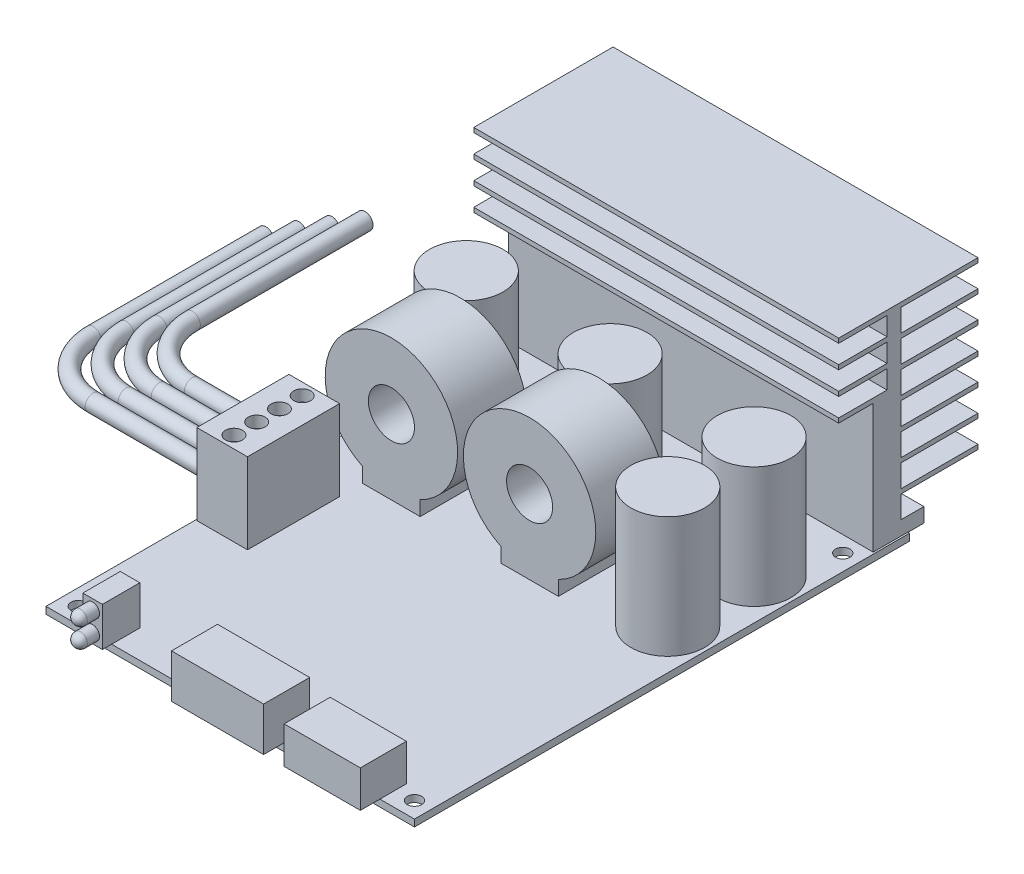
SolidWorks part; units mm, degrees
ref_plane "Front Plane" through (0, 0, 0) normal (0, 0, 1) x (1, 0, 0)
ref_plane "Top Plane" through (0, 0, 0) normal (0, 1, 0) x (1, 0, 0)
ref_plane "Right Plane" through (0, 0, 0) normal (1, 0, 0) x (0, 0, -1)
ref_plane "Plane1" through (0, 10.16, 0) normal (0, 1, 0) x (-1, 0, 0)
sketch "Sketch9" plane through (0, 0, 0) normal (0, 1, 0) x (1, 0, 0)
  line L1 (-40.64, -54.61) -> (40.64, -54.61)
  line L2 (-40.64, -54.61) -> (-40.64, 54.61)
  line L3 (-40.64, 54.61) -> (40.64, 54.61)
  line L4 (40.64, -54.61) -> (40.64, 54.61)
  circle A0 centre (37.084, -51.054) radius 1.5875
  circle A1 centre (37.084, 43.434) radius 1.5875
  circle A2 centre (-37.084, 43.434) radius 1.5875
  circle A3 centre (-37.084, -51.054) radius 1.5875
  point P4 (40.64, 0)
  point P5 (0, 54.61)
  dimension "D3" = 3.556
  dimension "D4" = 3.556
  dimension "D5" = 3.175
  dimension "D6" = 94.488
  dimension "D7" = 74.168
  dimension "D8" = 3.556
  dimension "D1" = 81.28
  dimension "D2" = 109.22
extrude "Boss-Extrude9" add sketch "Sketch9" along normal blind 1.524
sketch "Sketch2" plane through (0, 0, 0) normal (1, 0, 0) x (0, 0, -1)
  line L0 (39.37, 46.228) -> (70.104, 46.228)
  line L1 (70.104, 46.228) -> (70.104, 45.228)
  line L2 (70.104, 45.228) -> (53.086, 45.228)
  line L3 (53.086, 45.228) -> (53.086, 40.2844)
  line L4 (53.086, 40.2844) -> (70.104, 40.2844)
  line L5 (70.104, 10.5664) -> (70.104, 9.5664)
  line L6 (53.086, 4.6482) -> (58.166, 4.6482)
  line L7 (50.038, 45.228) -> (50.038, 41.1427)
  line L8 (70.104, 40.2844) -> (70.104, 39.2844)
  line L9 (70.104, 39.2844) -> (53.086, 39.2844)
  line L10 (53.086, 39.2844) -> (53.086, 34.3408)
  line L11 (53.086, 34.3408) -> (70.104, 34.3408)
  line L12 (70.104, 34.3408) -> (70.104, 33.3408)
  line L13 (70.104, 33.3408) -> (53.086, 33.3408)
  line L14 (53.086, 33.3408) -> (53.086, 28.3972)
  line L15 (53.086, 28.3972) -> (70.104, 28.3972)
  line L16 (70.104, 28.3972) -> (70.104, 27.3972)
  line L17 (70.104, 27.3972) -> (53.086, 27.3972)
  line L18 (53.086, 27.3972) -> (53.086, 22.4536)
  line L19 (53.086, 22.4536) -> (70.104, 22.4536)
  line L20 (70.104, 22.4536) -> (70.104, 21.4536)
  line L21 (70.104, 21.4536) -> (53.086, 21.4536)
  line L22 (53.086, 21.4536) -> (53.086, 16.51)
  line L23 (53.086, 16.51) -> (70.104, 16.51)
  line L24 (70.104, 16.51) -> (70.104, 15.51)
  line L25 (70.104, 15.51) -> (53.086, 15.51)
  line L26 (53.086, 15.51) -> (53.086, 10.5664)
  line L27 (53.086, 10.5664) -> (70.104, 10.5664)
  line L28 (70.104, 9.5664) -> (53.086, 9.5664)
  line L29 (50.038, 45.228) -> (39.37, 45.228)
  line L30 (53.086, 9.5664) -> (53.086, 4.6482)
  line L31 (46.99, 1.4732) -> (58.166, 1.4732)
  line L32 (58.166, 1.4732) -> (58.166, 4.6482)
  line L33 (39.37, 45.228) -> (39.37, 46.228)
  line L34 (50.038, 41.1427) -> (39.37, 41.1427)
  line L35 (39.37, 41.1427) -> (39.37, 40.1427)
  line L36 (39.37, 40.1427) -> (50.038, 40.1427)
  line L37 (50.038, 36.0573) -> (39.37, 36.0573)
  line L38 (39.37, 36.0573) -> (39.37, 35.0573)
  line L39 (39.37, 29.972) -> (46.99, 29.972)
  line L40 (46.99, 29.972) -> (46.99, 1.4732)
  line L41 (50.038, 40.1427) -> (50.038, 36.0573)
  line L42 (39.37, 35.0573) -> (50.038, 35.0573)
  line L43 (50.038, 35.0573) -> (50.038, 30.972)
  line L44 (50.038, 30.972) -> (39.37, 30.972)
  line L45 (39.37, 30.972) -> (39.37, 29.972)
  dimension "D1" = 1
  dimension "D2" = 5.9436
  dimension "D3" = 17.018
  dimension "D4" = 6.096
  dimension "D5" = 3.175
  dimension "D6" = 7.62
  dimension "D7" = 46.228
  dimension "D8" = 3.048
  dimension "D9" = 10.668
  dimension "D10" = 16.256
  dimension "D11" = 1.4732
  dimension "D12" = 36.6616
  dimension "D13" = 11.176
extrude "Boss-Extrude2" add sketch "Sketch2" along normal mid plane 80.5 separate body
sketch "Sketch10" plane through (0, 1.524, 0) normal (0, 1, 0) x (1, 0, 0)
  line L1 (-8.636, -48.768) -> (11.684, -48.768)
  line L2 (-8.636, -48.768) -> (-8.636, -58.928)
  line L3 (-8.636, -58.928) -> (11.684, -58.928)
  line L4 (11.684, -48.768) -> (11.684, -58.928)
  line L5 (-40.64, -54.61) -> (40.64, -54.61) construction
  line L6 (40.64, -54.61) -> (40.64, 54.61) construction
  point P4 (1.524, -48.768)
  dimension "D1" = 4.318
  dimension "D2" = 10.16
  dimension "D3" = 20.32
  dimension "D4" = 1.524
  dimension "D5" = 49.276
extrude "Boss-Extrude10" add sketch "Sketch10" along normal blind 9.652
sketch "Sketch11" plane through (0, 1.524, 0) normal (0, 1, 0) x (1, 0, 0)
  line L1 (16.2052, -48.768) -> (33.02, -48.768)
  line L2 (16.2052, -48.768) -> (16.2052, -58.928)
  line L3 (16.2052, -58.928) -> (33.02, -58.928)
  line L4 (33.02, -48.768) -> (33.02, -58.928)
  line L5 (-40.64, -54.61) -> (40.64, -54.61) construction
  line L6 (40.64, -54.61) -> (40.64, 54.61) construction
  point P4 (24.6126, -48.768)
  dimension "D1" = 7.62
  dimension "D2" = 16.8148
  dimension "D3" = 4.318
  dimension "D4" = 10.16
extrude "Boss-Extrude11" add sketch "Sketch11" along normal blind 8.128
sketch "Sketch12" plane through (0, 1.524, 0) normal (0, 1, 0) x (1, 0, 0)
  line L0 (-40.64, -54.61) -> (-40.64, 54.61) construction
  line L1 (-40.386, -1.27) -> (-29.21, -1.27)
  line L2 (-40.386, -1.27) -> (-40.386, -21.59)
  line L3 (-40.386, -21.59) -> (-29.21, -21.59)
  line L4 (-29.21, -1.27) -> (-29.21, -21.59)
  line L5 (-40.386, -1.27) -> (-50.546, -18.8676) construction
  point P4 (-40.386, -11.43)
  dimension "D1" = 11.43
  dimension "D2" = 20.32
  dimension "D3" = 11.176
  dimension "D4" = 0.254
  dimension "D5" = 30
extrude "Boss-Extrude12" add sketch "Sketch12" along normal blind 17.78
sketch "Sketch8" plane through (0, 19.304, 0) normal (0, 1, 0) x (1, 0, 0)
  line L0 (-34.8332, -3.9052) -> (-34.8332, -8.9217) construction
  line L1 (-34.8332, -8.9217) -> (-34.8332, -13.9382) construction
  line L2 (-34.8332, -13.9382) -> (-34.8332, -18.9547) construction
  line L3 (-40.386, -1.27) -> (-40.386, -21.59) construction
  circle A0 centre (-34.8332, -3.9052) radius 1.8733
  circle A1 centre (-34.8332, -8.9217) radius 1.8733
  circle A2 centre (-34.8332, -13.9382) radius 1.8733
  circle A3 centre (-34.8332, -18.9547) radius 1.8733
  point P8 (-34.8332, -11.43)
  dimension "D1" = 3.7465
  dimension "D2" = 1.27
  dimension "D3" = 5.5529
extrude "Cut-Extrude1" cut sketch "Sketch8" against normal blind 2.54
sketch "Sketch14" plane through (0, 10.16, 0) normal (0, 1, 0) x (-1, 0, 0)
  line L0 (40.386, 19.05) -> (65.786, 19.05)
  line L1 (78.486, 6.35) -> (78.486, -31.75)
  line L2 (40.386, 1.27) -> (40.386, 21.59) construction
  arc A0 (65.786, 19.05) -> (78.486, 6.35) centre (65.786, 6.35) cw
  dimension "D4" = 12.7
  dimension "D1" = 7.62
  dimension "D2" = 38.1
  dimension "D3" = 50.8
sketch "Sketch15" plane through (-40.386, 0, 0) normal (-1, 0, 0) x (0, 0, 1)
  circle A0 centre (19.05, 10.16) radius 1.778
  dimension "D1" = 3.556
sweep "Sweep1" add profiles "Sketch15" path "Sketch14"
pattern_linear "LPattern1" count 4 spacing 5.334 along (0.5, 0, -0.866) of "Sweep1"
sketch "Sketch1" plane through (0, 0, 0) normal (0, 0, 1) x (1, 0, 0)
  line L1 (-49, -12.7) -> (49, -12.7)
  line L2 (-49, -12.7) -> (-49, 51.8)
  line L3 (-49, 51.8) -> (49, 51.8)
  line L4 (49, -12.7) -> (49, 51.8)
  point P4 (0, 51.8)
  point P5 (-49, 19.55)
  dimension "D1" = 98
  dimension "D2" = 64.5
  dimension "D3" = 12.7
extrude "Boss-Extrude1" [suppressed] add sketch "Sketch1" along normal mid plane 116
sketch "Sketch3" [suppressed] plane through (49, 0, 0) normal (1, 0, 0) x (0, 0, -1)
  line L0 (58, -12.7) -> (58, 51.8) construction
  line L1 (-58, -12.7) -> (58, -12.7) construction
  circle A0 centre (-44.7176, -4.4831) radius 3.4036
  circle A1 centre (36.7529, -4.4831) radius 3.4036
  circle A2 centre (49.3005, 21.5392) radius 3.4036
  dimension "D6" = 6.8072
  dimension "D1" = 8.6995
  dimension "D2" = 34.2392
  dimension "D3" = 8.2169
  dimension "D4" = 21.2471
  dimension "D5" = 81.4705
extrude "Boss-Extrude3" [suppressed] add sketch "Sketch3" along normal blind 2.1336
sketch "Sketch4" [suppressed] plane through (-49, 0, 0) normal (-1, 0, 0) x (0, 0, 1)
  circle A0 centre (-49.3005, 21.5392) radius 3.4036 construction
  circle A1 centre (44.7176, -4.4831) radius 3.4036 construction
  circle A2 centre (-36.7529, -4.4831) radius 3.4036 construction
  circle A3 centre (-49.3005, 21.5392) radius 3.4036
  circle A4 centre (44.7176, -4.4831) radius 3.4036
  circle A5 centre (-36.7529, -4.4831) radius 3.4036
extrude "Boss-Extrude4" [suppressed] add sketch "Sketch4" along normal blind 2.1336
sketch "Sketch5" [suppressed] plane through (-49, 0, 0) normal (-1, 0, 0) x (0, 0, 1)
  line L0 (4.152, 10.8712) -> (16.09, 10.8712) construction
  line L1 (4.152, 18.4912) -> (16.09, 18.4912)
  line L2 (4.152, 3.2512) -> (16.09, 3.2512)
  line L3 (58, -12.7) -> (-58, -12.7) construction
  line L4 (58, 51.8) -> (58, -12.7) construction
  line L5 (4.152, 15.3162) -> (16.09, 15.3162)
  line L6 (4.152, 6.4262) -> (16.09, 6.4262)
  arc A0 (4.152, 18.4912) -> (4.152, 3.2512) centre (4.152, 10.8712) ccw
  arc A1 (16.09, 3.2512) -> (16.09, 18.4912) centre (16.09, 10.8712) ccw
  arc A2 (16.09, 6.4262) -> (16.09, 15.3162) centre (16.09, 10.8712) ccw
  arc A3 (4.152, 15.3162) -> (4.152, 6.4262) centre (4.152, 10.8712) ccw
  point P2 (10.121, 10.8712)
  dimension "D4" = 34.29
  dimension "D1" = 15.24
  dimension "D2" = 11.938
  dimension "D3" = 15.9512
  dimension "D5" = 3.175
extrude "Boss-Extrude5" [suppressed] add sketch "Sketch5" along normal blind 3.175
sketch "Sketch7" [suppressed] plane through (0, -12.7, 0) normal (0, -1, 0) x (1, 0, 0)
  line L0 (-49, 58) -> (49, 58) construction
  line L1 (-27.918, -33.186) -> (29.0034, -33.186) construction
  line L2 (-27.918, -33.186) -> (-27.918, 39.204) construction
  line L3 (-27.918, 39.204) -> (29.0034, 39.204) construction
  line L4 (29.0034, -33.186) -> (29.0034, 39.204) construction
  line L5 (-49, 58) -> (-49, -58) construction
  circle A0 centre (-27.918, 39.204) radius 3.4036
  circle A1 centre (29.0034, 39.204) radius 3.4036
  circle A2 centre (-27.918, -33.186) radius 3.4036
  circle A3 centre (29.0034, -33.186) radius 3.4036
  point P8 (0.5427, 39.204)
  point P9 (-27.918, 3.009)
  dimension "D5" = 6.8072
  dimension "D1" = 56.9214
  dimension "D2" = 72.39
  dimension "D3" = 18.796
  dimension "D4" = 21.082
extrude "Boss-Extrude7" [suppressed] add sketch "Sketch7" along normal blind 6.35
sketch "Sketch16" plane through (0, 1.524, 0) normal (0, 1, 0) x (1, 0, 0)
  circle A0 centre (-31.75, 29.21) radius 8.128
  circle A1 centre (0, 29.21) radius 8.128
  circle A2 centre (31.75, 29.21) radius 8.128
  circle A3 centre (31.75, 10.16) radius 8.128
  dimension "D1" = 16.256
  dimension "D2" = 19.05
  dimension "D3" = 31.75
  dimension "D4" = 31.75
  dimension "D5" = 29.21
extrude "Boss-Extrude13" add sketch "Sketch16" along normal blind 26.67
sketch "Sketch17" plane through (0, 0, 0) normal (0, 0, 1) x (1, 0, 0)
  line L0 (1.27, 0.762) -> (13.97, 0.762)
  line L1 (13.97, 0.762) -> (13.97, 4.7547)
  line L2 (1.27, 0.762) -> (1.27, 4.7547)
  line L3 (-7.62, 25.6569) -> (-7.62, 6.3091) construction
  line L4 (-16.51, 0.762) -> (-16.51, 4.7547)
  line L5 (-29.21, 0.762) -> (-29.21, 4.7547)
  line L6 (-16.51, 0.762) -> (-29.21, 0.762)
  arc A0 (13.97, 4.7547) -> (1.27, 4.7547) centre (7.62, 17.907) ccw
  circle A1 centre (7.62, 17.907) radius 5.08
  circle A2 centre (-22.86, 17.907) radius 5.08
  arc A3 (-29.21, 4.7547) -> (-16.51, 4.7547) centre (-22.86, 17.907) cw
  point P7 (7.62, 0.762)
  point P14 (-22.86, 0.762)
  dimension "D1" = 10.16
  dimension "D2" = 14.605
  dimension "D5" = 31.75
  dimension "D3" = 12.7
  dimension "D4" = 0.762
  dimension "D6" = 7.62
  dimension "D7" = 30.48
extrude "Boss-Extrude14" add sketch "Sketch17" against normal blind 15.24 from offset 3.81 offset against normal yes
sketch "Sketch18" plane through (0, 1.524, 0) normal (0, 1, 0) x (1, 0, 0)
  line L0 (-40.64, -54.61) -> (-40.64, 54.61) construction
  line L1 (-30.48, -48.387) -> (-26.162, -48.387)
  line L2 (-30.48, -48.387) -> (-30.48, -56.642)
  line L3 (-30.48, -56.642) -> (-26.162, -56.642)
  line L4 (-26.162, -48.387) -> (-26.162, -56.642)
  line L5 (-40.64, -54.61) -> (40.64, -54.61) construction
  point P8 (-28.321, -56.642)
  dimension "D1" = 10.16
  dimension "D2" = 4.318
  dimension "D3" = 8.255
  dimension "D4" = 2.032
extrude "Boss-Extrude15" add sketch "Sketch18" along normal blind 8.636
sketch "Sketch19" plane through (0, 0, 56.642) normal (0, 0, 1) x (1, 0, 0)
  line L0 (-30.48, 1.524) -> (-26.162, 1.524) construction
  circle A0 centre (-28.321, 8.001) radius 1.524
  circle A1 centre (-28.321, 3.683) radius 1.524
  dimension "D1" = 3.048
  dimension "D3" = 4.318
  dimension "D2" = 2.159
extrude "Boss-Extrude16" add sketch "Sketch19" along normal blind 2.6924
dome "Dome1" faces to dome 1 distance 1.524 reverse direction no elliptical dome no face at (-26.797, 8.001, 59.3344) parameters "D1"=1.524
dome "Dome2" faces to dome 1 distance 1.524 reverse direction no elliptical dome no face at (-26.797, 3.683, 59.3344) parameters "D1"=1.524
sketch "Sketch20" plane through (0, 0, 0) normal (0, -1, 0) x (1, 0, 0)
  line L0 (-40.64, 54.61) -> (40.64, 54.61) construction
  line L1 (1.016, -21.336) -> (-14.478, -21.336)
  line L2 (1.016, -21.336) -> (1.016, -7.874)
  line L3 (1.016, -7.874) -> (-14.478, -7.874)
  line L4 (-14.478, -21.336) -> (-14.478, -7.874)
  line L5 (-40.64, 54.61) -> (-40.64, -54.61) construction
  dimension "D1" = 75.946
  dimension "D2" = 13.462
  dimension "D3" = 15.494
  dimension "D4" = 26.162
extrude "Boss-Extrude17" add sketch "Sketch20" along normal blind 6.604
